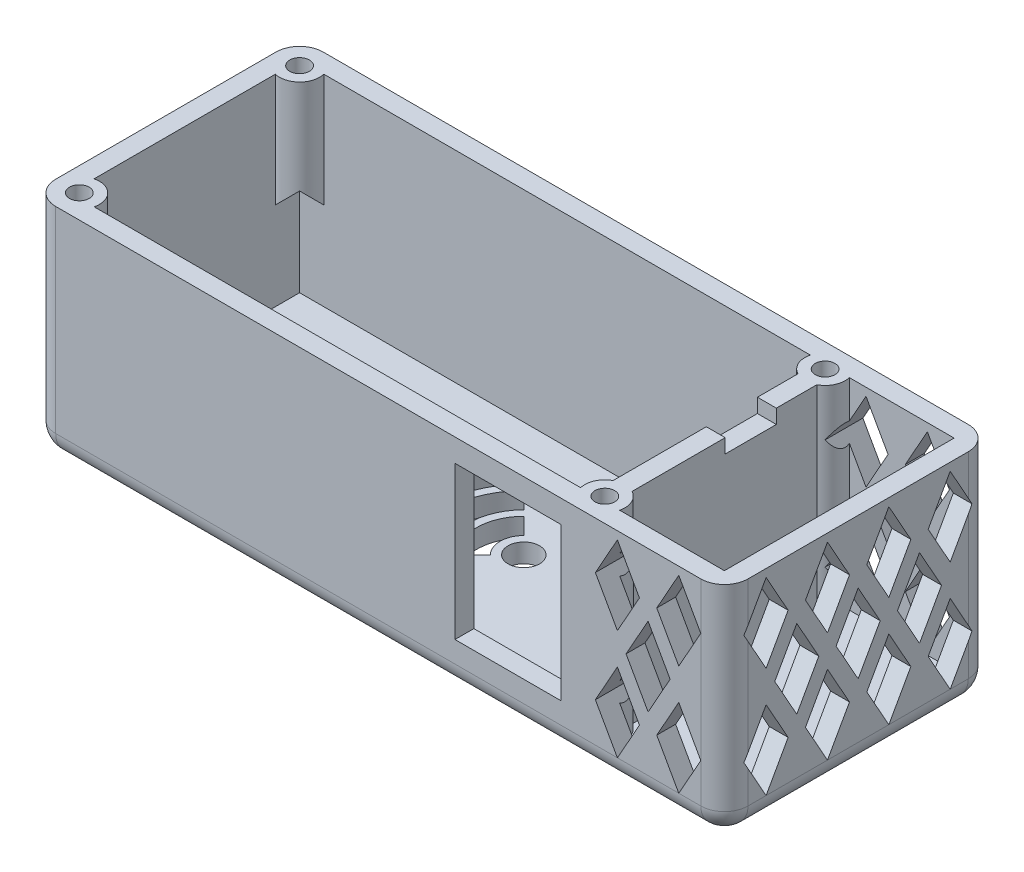
SolidWorks part; units mm, degrees
ref_plane "Front Plane" through (0, 0, 0) normal (0, 0, 1) x (1, 0, 0)
ref_plane "Top Plane" through (0, 0, 0) normal (0, 1, 0) x (1, 0, 0)
ref_plane "Right Plane" through (0, 0, 0) normal (1, 0, 0) x (0, 0, -1)
sketch "Sketch1" plane through (0, 0, 0) normal (0, 1, 0) x (1, 0, 0)
  line L1 (-35.5, 17) -> (35.5, 17)
  line L2 (-35.5, 17) -> (-35.5, -17)
  line L3 (-35.5, -17) -> (35.5, -17)
  line L4 (35.5, 17) -> (35.5, -17)
  line L5 (-35.5, 17) -> (35.5, -17) construction
  line L6 (-35.5, -17) -> (35.5, 17) construction
  point P0 (0, 0)
  dimension "D1" = 34
  dimension "D2" = 71
extrude "Boss-Extrude1" add sketch "Sketch1" along normal blind 28
shell "Shell1" thickness 2.4 removed face at (0, 28, 0)
sketch "Sketch2" plane through (0, 28, 0) normal (0, 1, 0) x (1, 0, 0)
  line L0 (35.5, -17) -> (35.5, 17) construction
  line L1 (33.1, 0.1) -> (35.5, 0.1)
  line L2 (33.1, 0.1) -> (33.1, 6.6)
  line L3 (33.1, 6.6) -> (35.5, 6.6)
  line L4 (35.5, 0.1) -> (35.5, 6.6)
  line L5 (33.1, -14.6) -> (33.1, 14.6) construction
  line L7 (33.1, 14.6) -> (-33.1, 14.6) construction
  dimension "D1" = 6.5
  dimension "D2" = 8
extrude "Cut-Extrude1" cut sketch "Sketch2" against normal blind 1.8
sketch "Sketch3" plane through (0, 0, 0) normal (0, -1, 0) x (1, 0, 0)
  line L0 (35.5, 17) -> (35.5, -17) construction
  line L1 (35.5, 17) -> (52.5, 17)
  line L2 (35.5, 17) -> (35.5, -17)
  line L3 (35.5, -17) -> (52.5, -17)
  line L4 (52.5, 17) -> (52.5, -17)
  line L6 (-35.5, 17) -> (35.5, 17) construction
  line L7 (35.5, -17) -> (-35.5, -17) construction
  dimension "D1" = 17
extrude "Boss-Extrude2" add sketch "Sketch3" against normal up to surface (28 mm away) up to face at (11.4333, 28, -1.1167)
sketch "Sketch4" plane through (0, 28, 0) normal (0, 1, 0) x (1, 0, 0)
  line L3 (35.5, -14.6) -> (50.1, -14.6)
  line L8 (35.5, -14.6) -> (35.5, 14.6)
  line L9 (35.5, 14.6) -> (50.1, 14.6)
  line L10 (50.1, -14.6) -> (50.1, 14.6)
  line L11 (33.1, -14.6) -> (33.1, 0.1) construction
  line L12 (52.5, 17) -> (52.5, -17) construction
  line L13 (52.5, 17) -> (-35.5, 17) construction
  line L14 (-35.5, -17) -> (52.5, -17) construction
  dimension "D1" = 2.4
  dimension "D2" = 2.4
  dimension "D3" = 2.4
  dimension "D4" = 2.4
extrude "Cut-Extrude2" cut sketch "Sketch4" against normal offset from surface (25.6 mm away) 2.4 up to face at (8.5, 0, 0)
sketch "Sketch5" plane through (0, 0, 0) normal (0, -1, 0) x (1, 0, 0)
  line L1 (7.8787, 2.1213) -> (5.7574, 4.2426)
  line L3 (2.2218, -7.7782) -> (0.1005, -9.8995)
  line L4 (5.0503, -4.9497) -> (2.9289, -7.0711)
  line L5 (7.8787, -2.1213) -> (5.7574, -4.2426)
  line L6 (5.0503, 4.9497) -> (2.9289, 7.0711)
  line L7 (2.2218, 7.7782) -> (0.1005, 9.8995)
  circle A0 centre (10, 0) radius 2
  arc A1 (7.8787, 2.1213) -> (7.8787, -2.1213) centre (10, 0) ccw
  arc A2 (5.7574, 4.2426) -> (5.7574, -4.2426) centre (10, 0) ccw
  arc A3 (5.0503, 4.9497) -> (5.0503, -4.9497) centre (10, 0) ccw
  arc A4 (2.9289, 7.0711) -> (2.9289, -7.0711) centre (10, 0) ccw
  arc A5 (2.2218, 7.7782) -> (2.2218, -7.7782) centre (10, 0) ccw
  arc A6 (0.1005, 9.8995) -> (0.1005, -9.8995) centre (10, 0) ccw
  dimension "D2" = 4
  dimension "D3" = 6
  dimension "D4" = 12
  dimension "D5" = 14
  dimension "D6" = 20
  dimension "D7" = 22
  dimension "D8" = 28
  dimension "D1" = 10
extrude "Cut-Extrude3" cut sketch "Sketch5" against normal up to next
sketch "Sketch7" plane through (52.5, 0, 0) normal (1, 0, 0) x (0, 0, -1)
  line L4 (17, 28) -> (17, 0) construction
  line L5 (17, 0) -> (-17, 0) construction
  line L21 (10.6, 8) -> (7.8, 3) [skipped]
  line L22 (7.8, 13) -> (10.6, 8) [skipped]
  line L23 (11.7, 13) -> (8.9, 8)
  line L24 (11.7, 13) -> (14.5, 8)
  line L25 (14.5, 8) -> (11.7, 3)
  line L26 (8.9, 8) -> (11.7, 3)
  line L27 (11.7, 13) -> (11.7, 3) construction
  line L28 (14.5, 8) -> (8.9, 8) construction
  line L29 (7.8, 13) -> (5, 8) [skipped]
  line L30 (5, 8) -> (7.8, 3) [skipped]
  line L31 (6.7, 8) -> (3.9, 3)
  line L32 (3.9, 13) -> (6.7, 8)
  line L33 (3.9, 13) -> (1.1, 8)
  line L34 (1.1, 8) -> (3.9, 3)
  line L35 (2.8, 8) -> (0, 3) [skipped]
  line L36 (0, 13) -> (2.8, 8) [skipped]
  line L37 (0, 13) -> (-2.8, 8) [skipped]
  line L38 (-2.8, 8) -> (0, 3) [skipped]
  line L39 (-1.1, 8) -> (-3.9, 3)
  line L40 (-3.9, 13) -> (-1.1, 8)
  line L41 (-3.9, 13) -> (-6.7, 8)
  line L42 (-6.7, 8) -> (-3.9, 3)
  line L43 (-5, 8) -> (-7.8, 3) [skipped]
  line L44 (-7.8, 13) -> (-5, 8) [skipped]
  line L45 (-7.8, 13) -> (-10.6, 8) [skipped]
  line L46 (-10.6, 8) -> (-7.8, 3) [skipped]
  line L47 (-8.9, 8) -> (-11.7, 3)
  line L48 (-11.7, 13) -> (-8.9, 8)
  line L49 (-11.7, 13) -> (-14.5, 8)
  line L50 (-14.5, 8) -> (-11.7, 3)
  line L51 (10.6, 15) -> (7.8, 10)
  line L52 (7.8, 20) -> (10.6, 15)
  line L53 (7.8, 20) -> (5, 15)
  line L54 (5, 15) -> (7.8, 10)
  line L55 (6.7, 15) -> (3.9, 10) [skipped]
  line L56 (3.9, 20) -> (6.7, 15) [skipped]
  line L57 (3.9, 20) -> (1.1, 15) [skipped]
  line L58 (1.1, 15) -> (3.9, 10) [skipped]
  line L59 (2.8, 15) -> (0, 10)
  line L60 (0, 20) -> (2.8, 15)
  line L61 (0, 20) -> (-2.8, 15)
  line L62 (-2.8, 15) -> (0, 10)
  line L63 (-1.1, 15) -> (-3.9, 10) [skipped]
  line L64 (-3.9, 20) -> (-1.1, 15) [skipped]
  line L65 (-3.9, 20) -> (-6.7, 15) [skipped]
  line L66 (-6.7, 15) -> (-3.9, 10) [skipped]
  line L67 (-5, 15) -> (-7.8, 10)
  line L68 (-7.8, 20) -> (-5, 15)
  line L69 (-7.8, 20) -> (-10.6, 15)
  line L70 (-10.6, 15) -> (-7.8, 10)
  line L71 (-8.9, 15) -> (-11.7, 10) [skipped]
  line L72 (-11.7, 20) -> (-8.9, 15) [skipped]
  line L73 (-11.7, 20) -> (-14.5, 15) [skipped]
  line L74 (-14.5, 15) -> (-11.7, 10) [skipped]
  line L75 (10.6, 22) -> (7.8, 17) [skipped]
  line L76 (7.8, 27) -> (10.6, 22) [skipped]
  line L77 (7.8, 27) -> (5, 22) [skipped]
  line L78 (5, 22) -> (7.8, 17) [skipped]
  line L79 (6.7, 22) -> (3.9, 17)
  line L80 (3.9, 27) -> (6.7, 22)
  line L81 (3.9, 27) -> (1.1, 22)
  line L82 (1.1, 22) -> (3.9, 17)
  line L83 (2.8, 22) -> (0, 17) [skipped]
  line L84 (0, 27) -> (2.8, 22) [skipped]
  line L85 (0, 27) -> (-2.8, 22) [skipped]
  line L86 (-2.8, 22) -> (0, 17) [skipped]
  line L87 (-1.1, 22) -> (-3.9, 17)
  line L88 (-3.9, 27) -> (-1.1, 22)
  line L89 (-3.9, 27) -> (-6.7, 22)
  line L90 (-6.7, 22) -> (-3.9, 17)
  line L91 (-5, 22) -> (-7.8, 17) [skipped]
  line L92 (-7.8, 27) -> (-5, 22) [skipped]
  line L93 (-7.8, 27) -> (-10.6, 22) [skipped]
  line L94 (-10.6, 22) -> (-7.8, 17) [skipped]
  line L95 (-8.9, 22) -> (-11.7, 17)
  line L96 (-11.7, 27) -> (-8.9, 22)
  line L97 (-11.7, 27) -> (-14.5, 22)
  line L98 (-14.5, 22) -> (-11.7, 17)
  line L99 (14.5, 15) -> (11.7, 10) [skipped]
  line L100 (11.7, 20) -> (14.5, 15) [skipped]
  line L101 (11.7, 20) -> (8.9, 15) [skipped]
  line L102 (8.9, 15) -> (11.7, 10) [skipped]
  line L103 (14.5, 22) -> (11.7, 17)
  line L104 (11.7, 27) -> (14.5, 22)
  line L105 (11.7, 27) -> (8.9, 22)
  line L106 (8.9, 22) -> (11.7, 17)
  point P0 (11.7, 8)
  dimension "D1" = 5.6
  dimension "D2" = 10
  dimension "D3" = 3
  dimension "D4" = 2.5
  dimension "D5" = 7
  dimension "D6" = 3
extrude "Cut-Extrude4" cut sketch "Sketch7" against normal up to next
sketch "Sketch8" plane through (0, 0, 14.6) normal (0, 0, -1) x (-1, 0, 0)
  line L32 (-18.25, 25.1) -> (-31.75, 25.1)
  line L33 (-18.25, 25.1) -> (-18.25, 5.7)
  line L34 (-18.25, 5.7) -> (-31.75, 5.7)
  line L35 (-31.75, 25.1) -> (-31.75, 5.7)
  line L36 (-18.25, 25.1) -> (-31.75, 5.7) construction
  line L37 (-18.25, 5.7) -> (-31.75, 25.1) construction
  line L40 (-17.5, 25.5) -> (-17.5, 5.3) construction
  line L41 (-32.5, 5.3) -> (-32.5, 25.5) construction
  line L42 (-32.1, 25.9) -> (-17.9, 25.9) construction
  line L43 (-17.9, 4.9) -> (-32.1, 4.9) construction
  point P58 (-25, 15.4)
  dimension "D1" = 0.75
  dimension "D2" = 0.75
  dimension "D3" = 0.8
  dimension "D4" = 0.8
extrude "Cut-Extrude5" cut sketch "Sketch8" against normal up to next
fillet "Fillet1" radius 3 4 edges at (-35.5, 14, 17) (-35.5, 14, -17) (52.5, 14, -17) (52.5, 14, 17)
fillet "Fillet2" radius 3 8 edges at (-34.6213, 0, 16.1213) (-35.5, 0, 0) (-34.6213, 0, -16.1213) (8.5, 0, -17) (51.6213, 0, -16.1213) (52.5, 0, 0) (51.6213, 0, 16.1213) (8.5, 0, 17)
sketch "Sketch11" plane through (0, 28, 0) normal (0, 1, 0) x (1, 0, 0)
  line L0 (35.5, -14.6) -> (33.1, -14.6) construction
  line L1 (34.3, -27.8091) -> (34.3, -26.1547) construction
  line L6 (-32.5, -17) -> (49.5, -17) construction
  line L7 (49.5, 17) -> (-32.5, 17) construction
  circle A0 centre (34.3, -14) radius 2.5547
  circle A1 centre (34.3, 14) radius 2.5547
  point P13 (34.3, -14.6)
  dimension "D1" = 5.1094
  dimension "D2" = 3
  dimension "D3" = 3
extrude "Boss-Extrude3" add sketch "Sketch11" against normal up to surface (25.6 mm away) up to face at (42.8, 2.4, 0)
sketch "Sketch14" plane through (0, 28, -28) normal (0, -1, 0) x (1, 0, 0)
  circle A2 centre (-32.5, 42) radius 2.5547
  circle A3 centre (-32.5, 14) radius 2.5547
  arc A5 (-35.5, 14) -> (-32.5, 11) centre (-32.5, 14) ccw construction
  arc A6 (-32.5, 45) -> (-35.5, 42) centre (-32.5, 42) ccw construction
extrude "Boss-Extrude4" add sketch "Sketch14" along normal blind 12
chamfer "Chamfer1" distance 2.4 angle 45 4 edges at (-33.1, 16, -13.0584) (-31.5584, 16, -14.6) (-31.5584, 16, 14.6) (-33.1, 16, 13.0584)
sketch "Sketch10" plane through (0, 0, 17) normal (0, 0, 1) x (1, 0, 0)
  line L0 (49.5, 0) -> (-32.5, 0) construction
  line L21 (45.6, 8) -> (42.8, 3) [skipped]
  line L22 (42.8, 13) -> (45.6, 8) [skipped]
  line L23 (46.7, 13) -> (43.9, 8)
  line L24 (46.7, 13) -> (49.5, 8)
  line L25 (49.5, 8) -> (46.7, 3)
  line L26 (43.9, 8) -> (46.7, 3)
  line L27 (46.7, 13) -> (46.7, 3) construction
  line L28 (49.5, 8) -> (43.9, 8) construction
  line L29 (42.8, 13) -> (40, 8) [skipped]
  line L30 (40, 8) -> (42.8, 3) [skipped]
  line L31 (41.7, 8) -> (38.9, 3)
  line L32 (38.9, 13) -> (41.7, 8)
  line L33 (38.9, 13) -> (36.1, 8)
  line L34 (36.1, 8) -> (38.9, 3)
  line L35 (37.8, 8) -> (35, 3) [skipped]
  line L36 (35, 13) -> (37.8, 8) [skipped]
  line L37 (35, 13) -> (32.2, 8) [skipped]
  line L38 (32.2, 8) -> (35, 3) [skipped]
  line L43 (30, 8) -> (27.2, 3) [skipped]
  line L44 (27.2, 13) -> (30, 8) [skipped]
  line L45 (27.2, 13) -> (24.4, 8) [skipped]
  line L46 (24.4, 8) -> (27.2, 3) [skipped]
  line L51 (45.6, 15) -> (42.8, 10)
  line L52 (42.8, 20) -> (45.6, 15)
  line L53 (42.8, 20) -> (40, 15)
  line L54 (40, 15) -> (42.8, 10)
  line L55 (41.7, 15) -> (38.9, 10) [skipped]
  line L56 (38.9, 20) -> (41.7, 15) [skipped]
  line L57 (38.9, 20) -> (36.1, 15) [skipped]
  line L58 (36.1, 15) -> (38.9, 10) [skipped]
  line L63 (33.9, 15) -> (31.1, 10) [skipped]
  line L64 (31.1, 20) -> (33.9, 15) [skipped]
  line L65 (31.1, 20) -> (28.3, 15) [skipped]
  line L66 (28.3, 15) -> (31.1, 10) [skipped]
  line L71 (26.1, 15) -> (23.3, 10) [skipped]
  line L72 (23.3, 20) -> (26.1, 15) [skipped]
  line L73 (23.3, 20) -> (20.5, 15) [skipped]
  line L74 (20.5, 15) -> (23.3, 10) [skipped]
  line L75 (45.6, 22) -> (42.8, 17) [skipped]
  line L76 (42.8, 27) -> (45.6, 22) [skipped]
  line L77 (42.8, 27) -> (40, 22) [skipped]
  line L78 (40, 22) -> (42.8, 17) [skipped]
  line L79 (41.7, 22) -> (38.9, 17)
  line L80 (38.9, 27) -> (41.7, 22)
  line L81 (38.9, 27) -> (36.1, 22)
  line L82 (36.1, 22) -> (38.9, 17)
  line L83 (37.8, 22) -> (35, 17) [skipped]
  line L84 (35, 27) -> (37.8, 22) [skipped]
  line L85 (35, 27) -> (32.2, 22) [skipped]
  line L86 (32.2, 22) -> (35, 17) [skipped]
  line L91 (30, 22) -> (27.2, 17) [skipped]
  line L92 (27.2, 27) -> (30, 22) [skipped]
  line L93 (27.2, 27) -> (24.4, 22) [skipped]
  line L94 (24.4, 22) -> (27.2, 17) [skipped]
  line L99 (49.5, 15) -> (46.7, 10) [skipped]
  line L100 (46.7, 20) -> (49.5, 15) [skipped]
  line L101 (46.7, 20) -> (43.9, 15) [skipped]
  line L102 (43.9, 15) -> (46.7, 10) [skipped]
  line L103 (49.5, 22) -> (46.7, 17)
  line L104 (46.7, 27) -> (49.5, 22)
  line L105 (46.7, 27) -> (43.9, 22)
  line L106 (43.9, 22) -> (46.7, 17)
  line L107 (52.5, 21.1071) -> (52.5, 8.8929) construction
  line L108 (20.5, 22) -> (23.3, 17) [skipped]
  line L109 (33.9, 8) -> (31.1, 3) [skipped]
  line L110 (31.1, 13) -> (33.9, 8) [skipped]
  line L111 (31.1, 13) -> (28.3, 8) [skipped]
  line L112 (28.3, 8) -> (31.1, 3) [skipped]
  line L113 (26.1, 8) -> (23.3, 3) [skipped]
  line L114 (23.3, 13) -> (26.1, 8) [skipped]
  line L115 (23.3, 13) -> (20.5, 8) [skipped]
  line L116 (20.5, 8) -> (23.3, 3) [skipped]
  line L117 (37.8, 15) -> (35, 10) [skipped]
  line L118 (35, 20) -> (37.8, 15) [skipped]
  line L119 (35, 20) -> (32.2, 15) [skipped]
  line L120 (32.2, 15) -> (35, 10) [skipped]
  line L121 (30, 15) -> (27.2, 10) [skipped]
  line L122 (27.2, 20) -> (30, 15) [skipped]
  line L123 (27.2, 20) -> (24.4, 15) [skipped]
  line L124 (24.4, 15) -> (27.2, 10) [skipped]
  line L125 (33.9, 22) -> (31.1, 17) [skipped]
  line L126 (31.1, 27) -> (33.9, 22) [skipped]
  line L127 (31.1, 27) -> (28.3, 22) [skipped]
  line L128 (28.3, 22) -> (31.1, 17) [skipped]
  line L129 (26.1, 22) -> (23.3, 17) [skipped]
  line L130 (23.3, 27) -> (26.1, 22) [skipped]
  line L131 (23.3, 27) -> (20.5, 22) [skipped]
  point P0 (46.7, 8)
  dimension "D1" = 5.6
  dimension "D2" = 10
  dimension "D3" = 3
  dimension "D4" = 3
  dimension "D5" = 7
  dimension "D6" = 3
extrude "Cut-Extrude6" cut sketch "Sketch10" against normal through all
sketch "Sketch12" plane through (0, 28, 0) normal (0, 1, 0) x (1, 0, 0)
  circle A0 centre (34.3, 14) radius 1.25
  circle A1 centre (34.3, -14) radius 1.25
  circle A2 centre (-32.5, -14) radius 1.25
  circle A3 centre (-32.5, 14) radius 1.25
  arc A4 (35.5, 11.7447) -> (36.7832, 14.6) centre (34.3, 14) ccw construction
  arc A5 (33.1, -11.7447) -> (31.8168, -14.6) centre (34.3, -14) ccw construction
  arc A8 (-32.5, 17) -> (-35.5, 14) centre (-32.5, 14) ccw construction
  arc A9 (-35.5, -14) -> (-32.5, -17) centre (-32.5, -14) ccw construction
  dimension "D1" = 2.5
extrude "Cut-Extrude7" cut sketch "Sketch12" against normal blind 12
